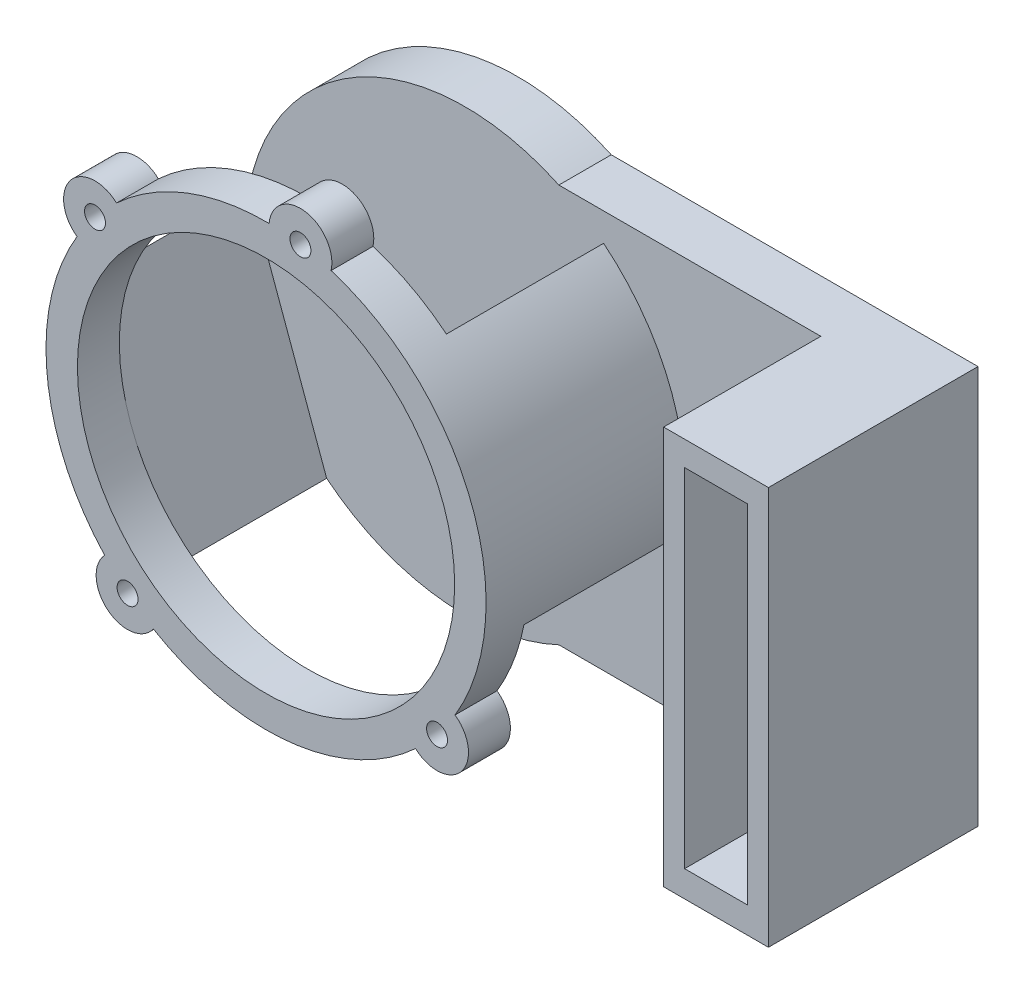
SolidWorks part; units mm, degrees
ref_plane "Piano frontale" through (0, 0, 0) normal (0, 0, 1) x (1, 0, 0)
ref_plane "Piano superiore" through (0, 0, 0) normal (0, 1, 0) x (1, 0, 0)
ref_plane "Piano destro" through (0, 0, 0) normal (1, 0, 0) x (0, 0, -1)
sketch "Schizzo1" plane through (0, 0, 0) normal (0, 0, 1) x (1, 0, 0)
  line L0 (12.3655, 11.6094) -> (47.3655, 11.6094) construction
  line L1 (12.3655, -26.3906) -> (47.3655, -26.3906)
  line L2 (47.3655, -26.3906) -> (47.3655, 11.6094)
  line L3 (47.3655, 11.6094) -> (12.3655, 11.6094)
  arc A2 (12.3655, 11.6094) -> (12.3655, -26.3906) centre (3.4212, -7.3906) ccw
  dimension "D1" = 35
  dimension "D4" = 35
  dimension "D3" = 42
  dimension "D2" = 38
extrude "Estrusione-Estrusione1" add sketch "Schizzo1" along normal mid plane 5
sketch "Schizzo2" plane through (0, 0, 2.5) normal (0, 0, 1) x (1, 0, 0)
  line L1 (37.3655, 11.6094) -> (47.3655, 11.6094)
  line L2 (37.3655, 11.6094) -> (37.3655, -26.3906)
  line L3 (37.3655, -26.3906) -> (47.3655, -26.3906)
  line L4 (47.3655, 11.6094) -> (47.3655, -26.3906)
  line L5 (37.3655, 11.6094) -> (47.3655, -26.3906) construction
  line L6 (37.3655, -26.3906) -> (47.3655, 11.6094) construction
  point P0 (42.3655, -7.3906)
  dimension "D1" = 10
extrude "Estrusione-Estrusione2" add sketch "Schizzo2" along normal blind 15
sketch "Schizzo3" plane through (0, 0, 17.5) normal (0, 0, 1) x (1, 0, 0)
  line L1 (39.3655, 9.2594) -> (45.3655, 9.2594)
  line L2 (39.3655, 9.2594) -> (39.3655, -23.8906)
  line L3 (39.3655, -23.8906) -> (45.3655, -23.8906)
  line L4 (45.3655, 9.2594) -> (45.3655, -23.8906)
  line L5 (39.3655, 9.2594) -> (45.3655, -23.8906) construction
  line L6 (39.3655, -23.8906) -> (45.3655, 9.2594) construction
  line L7 (47.3655, -26.3906) -> (47.3655, 11.6094) construction
  line L8 (37.3655, -26.3906) -> (47.3655, -26.3906) construction
  point P0 (42.3655, -7.3156)
  dimension "D1" = 6
  dimension "D2" = 2
  dimension "D3" = 33.15
  dimension "D4" = 2.5
extrude "Taglio-Estrusione1" cut sketch "Schizzo3" against normal blind 13
sketch "Schizzo5" plane through (0, 0, 2.5) normal (0, 0, 1) x (1, 0, 0)
  line L0 (37.3655, -7.3906) -> (-17.5788, -7.3906) construction
  line L1 (37.3655, 11.6094) -> (37.3655, -26.3906) construction
  line L3 (3.4212, -28.3906) -> (3.4212, 13.6094) construction
  arc A0 (12.3655, 11.6094) -> (12.3655, -26.3906) centre (3.4212, -7.3906) ccw construction
  circle A1 centre (3.4212, -7.3906) radius 21
extrude "Estrusione-Sottile1" add sketch "Schizzo5" along normal blind 19 thin thin type one direction reverse wall 3
sketch "Schizzo7" plane through (0, 0, 4.5) normal (0, 0, 1) x (1, 0, 0)
  line L0 (39.3655, -23.8906) -> (45.3655, -21.7068) construction
  line L1 (45.3655, -23.8906) -> (45.3655, 9.2594) construction
  line L2 (39.3655, -23.8906) -> (41.3406, -29.3173) construction
  line L3 (39.3655, -23.8906) -> (45.3655, -23.8906) construction
  line L4 (45.3655, -23.8906) -> (39.3655, -23.8906) construction
  dimension "D1" = 20
ref_plane "Piano1" through (-4.4069, 12.1079, 0) normal (-0.342, 0.9397, 0) x (0.9397, 0.342, 0)
sketch "Schizzo8" plane through (-4.4069, 12.1079, 0) normal (-0.342, 0.9397, 0) x (0.9397, 0.342, 0)
  line L6 (0.6872, -21.5) -> (0.6872, 2.5) construction
  line L7 (-20.3128, -21.5) -> (21.6872, -21.5) construction
  line L8 (15.5904, 2.5) -> (-20.3128, 2.5) construction
  line L9 (-17.3128, -17.5) -> (18.6872, -17.5)
  line L10 (18.6872, -17.5) -> (18.6872, -2.5)
  line L11 (2.5936, -2.5) -> (21.6872, -2.5) construction
  line L12 (18.6872, -2.5) -> (-17.3128, -2.5)
  line L13 (-17.3128, -2.5) -> (-17.3128, -17.5)
  dimension "D1" = 18
  dimension "D2" = 36
  dimension "D3" = 4
extrude "Taglio-Estrusione2" cut sketch "Schizzo8" against normal through all
sketch "Schizzo10" plane through (0, 0, 21.5) normal (0, 0, 1) x (1, 0, 0)
  line L0 (-9.7937, -23.7113) -> (16.6362, 8.93) construction
  line L1 (3.4212, -7.3906) -> (6.7054, 13.351) construction
  line L2 (19.7419, -20.6056) -> (-12.8995, 5.8243) construction
  circle A0 centre (3.4212, -7.3906) radius 21 construction
  circle A2 centre (-12.8995, 5.8243) radius 3
  circle A4 centre (19.7419, -20.6056) radius 3
  circle A5 centre (-9.7937, -23.7113) radius 3
  circle A7 centre (6.7054, 13.351) radius 3
  dimension "D2" = 6
  dimension "D3" = 6
  dimension "D5" = 6
  dimension "D1" = 42
  dimension "D6" = 30
extrude "Estrusione-Estrusione3" add sketch "Schizzo10" against normal blind 4
hole_wizard "Foro per Vite M1.6-1" positions "Schizzo3D1" profile "Schizzo11" hole size "M1.6" standard "ISO"
sketch3d "Schizzo3D1"
  point P0 (6.7054, 13.351, 21.5)
  point P3 (-12.8995, 5.8243, 21.5)
  point P6 (-9.7937, -23.7113, 21.5)
  point P9 (19.7419, -20.6056, 21.5)
sketch "Schizzo11" plane through (6.7054, 13.351, 21.5) normal (1, 0, 0) x (0, -1, 0)
  line L0 (0, 0) -> (0, 3.6009)
  line L1 (0, 3.6009) -> (1, 3)
  line L2 (1, 3) -> (1, 0)
  line L5 (1, 0) -> (0, 0)
  line L10 (0, 3.6009) -> (-1, 3) construction
  line L11 (0, -6.35) -> (0, 107.95) construction
  dimension "Hole Dia." = 2
  dimension "Hole Depth" = 3
  dimension "Drill Angle" = 118
